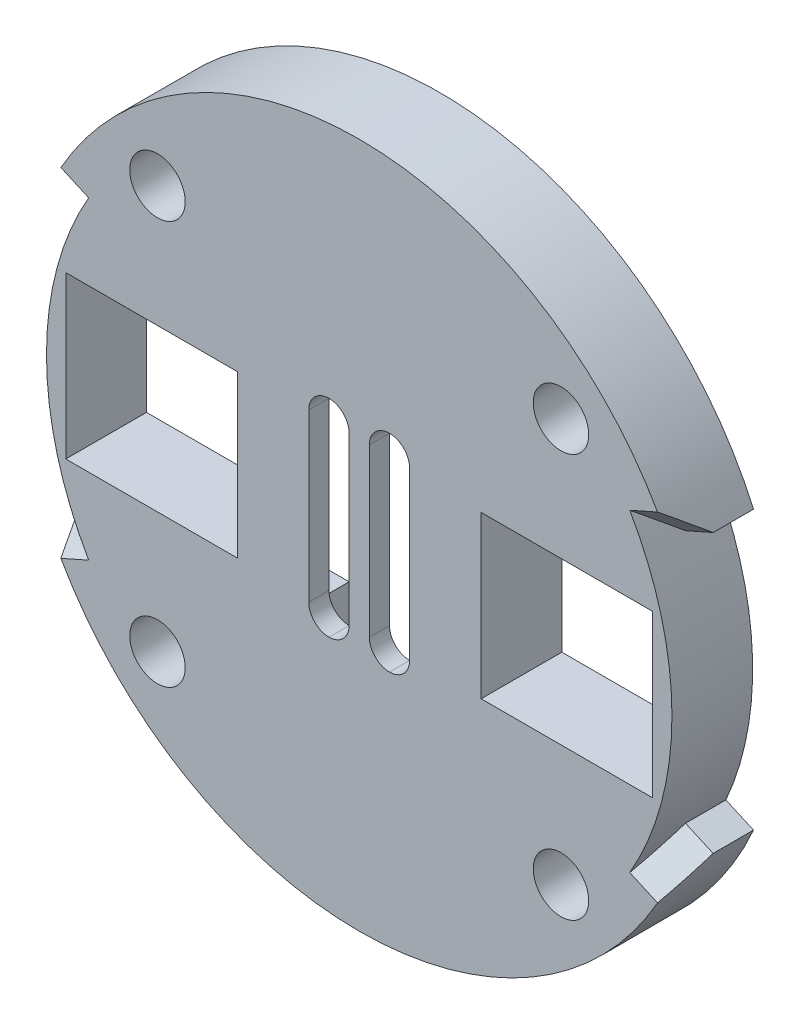
SolidWorks part; units mm, degrees
ref_plane "Front Plane" through (0, 0, 0) normal (0, 0, 1) x (1, 0, 0)
ref_plane "Top Plane" through (0, 0, 0) normal (0, 1, 0) x (1, 0, 0)
ref_plane "Right Plane" through (0, 0, 0) normal (1, 0, 0) x (0, 0, -1)
sketch "Sketch1" plane through (0, 0, 0) normal (0, 0, 1) x (1, 0, 0)
  line L2 (-32, 13.3673) -> (-29.2571, 12.1521)
  line L3 (-32, -14.1774) -> (-29.2571, -12.9622)
  line L4 (30.1714, -14.1774) -> (27.4286, -12.9622)
  line L5 (30.1714, 13.3673) -> (27.4286, 12.1521)
  arc A0 (-32, -14.1774) -> (30.1714, -14.1774) centre (-0.9143, -0.4051) ccw
  arc A1 (-29.2571, 12.1521) -> (-29.2571, -12.9622) centre (-0.9143, -0.4051) ccw
  arc A2 (27.4286, 12.1521) -> (27.4286, -12.9622) centre (-0.9143, -0.4051) cw
  arc A3 (30.1714, 13.3673) -> (-32, 13.3673) centre (-0.9143, -0.4051) ccw
  point P9 (-32, 0)
  dimension "D1" = 34
  dimension "D2" = 31
extrude "Boss-Extrude1" add sketch "Sketch1" along normal blind 8
ref_plane "Plane1" through (0, 0, 8) normal (0, 0, 1) x (1, 0, 0)
sketch "Sketch3" plane through (0, 0, 8) normal (0, 0, 1) x (1, 0, 0)
  line L0 (-0.9143, 33.5949) -> (-0.9143, -34.4051)
  line L1 (-31.9143, -0.4051) -> (30.0857, -0.4051)
  line L4 (-30, 7.5949) -> (-30, -8.4051)
  line L20 (-30, 7.5949) -> (-13, 7.5949)
  line L21 (-13, 7.5949) -> (-13, -8.4051)
  line L22 (-13, -8.4051) -> (-30, -8.4051)
  line L24 (11.1714, 7.5949) -> (11.1714, -8.4051)
  line L30 (28.1714, 7.5949) -> (11.1714, 7.5949)
  line L31 (28.1714, 7.5949) -> (28.1714, -8.4051)
  line L32 (11.1714, -8.4051) -> (28.1714, -8.4051)
  arc A0 (30.1714, 13.3673) -> (-32, 13.3673) centre (-0.9143, -0.4051) ccw construction
  arc A1 (-32, -14.1774) -> (30.1714, -14.1774) centre (-0.9143, -0.4051) ccw construction
  arc A3 (-29.2571, 12.1521) -> (-29.2571, -12.9622) centre (-0.9143, -0.4051) ccw construction
  arc A4 (27.4286, -12.9622) -> (27.4286, 12.1521) centre (-0.9143, -0.4051) ccw construction
  circle A5 centre (19.0857, 19.5949) radius 1.5
  circle A6 centre (19.0857, 19.5949) radius 2.75
  circle A7 centre (19.0857, -20.4051) radius 2.75
  circle A8 centre (-20.9143, 19.5949) radius 1.5
  circle A10 centre (-20.9143, 19.5949) radius 2.75
  circle A17 centre (19.0857, -20.4051) radius 1.5
  circle A18 centre (-20.9143, -20.4051) radius 2.75
  circle A19 centre (-20.9143, -20.4051) radius 1.5
  point P16 (0, 0)
  point P25 (-0.9143, -0.4051)
  dimension "D7" = 17
  dimension "D2" = 8
  dimension "D3" = 16
extrude "Cut-Extrude1" cut sketch "Sketch3" against normal blind 8 contours L4 | L4 | L24 L32 L31 L30 region at (-21.5, 3.5949, 8) region at (-21.5, -4.4051, 8)
extrude "Cut-Extrude3" cut sketch "Sketch3<5>" against normal blind 8 contours A8 | A19 | A17 | A5 region at (-20.9143, 19.5949, 8) region at (19.0857, -20.4051, 8) region at (-20.9143, -20.4051, 8)
sketch "Sketch3<5>" plane through (0, 0, 8) normal (0, 0, 1) x (1, 0, 0) same geometry as "Sketch3"
extrude "Cut-Extrude4" cut sketch "Sketch3<6>" against normal blind 6 contours A10 A8 | A6 A18 | A19 | A7 region at (16.4135, 19.5949, 8) region at (-23.5865, 19.5949, 8) region at (-23.5865, -20.4051, 8)
sketch "Sketch3<6>" plane through (0, 0, 8) normal (0, 0, 1) x (1, 0, 0) same geometry as "Sketch3"
chamfer "Chamfer1" distance 4 angle 40 4 edges at (28.8, -13.5698, 8) (28.8, 12.7597, 8) (-30.6286, -13.5698, 8) (-30.6286, 12.7597, 8) first distance on face at (28.8, -13.5698, 4) first distance on face at (28.8, 12.7597, 4) first distance on face at (-30.6286, -13.5698, 4) first distance on face at (-30.6286, 12.7597, 4)
sketch "Sketch4" plane through (0, 0, 0) normal (0, 0, 1) x (1, 0, 0)
  line L0 (-0.9143, 33.5949) -> (-0.9143, -34.4051)
  line L1 (8.0857, 29.5949) -> (-9.9143, 29.5949)
  line L2 (8.0857, 29.5949) -> (8.0857, -30.4051)
  line L3 (8.0857, -30.4051) -> (-9.9143, -30.4051)
  line L4 (-9.9143, 29.5949) -> (-9.9143, -30.4051)
  line L5 (28.1714, -0.4051) -> (-30, -0.4051)
  line L8 (28.1714, 7.5949) -> (28.1714, -8.4051) construction
  line L9 (-30, 7.5949) -> (-30, -8.4051) construction
  arc A0 (30.1714, 13.3673) -> (-32, 13.3673) centre (-0.9143, -0.4051) ccw construction
  arc A1 (-32, -14.1774) -> (30.1714, -14.1774) centre (-0.9143, -0.4051) ccw construction
  dimension "D1" = 18
  dimension "D2" = 60
  dimension "D3" = 9
  dimension "D4" = 30
extrude "Cut-Extrude6" cut sketch "Sketch4" along normal blind 6 contours L5 L0 L1 L4 | L5 L2 L1 L0 | L5 L0 L3 L2 | L5 L4 L3 L0 region at (3.5857, 14.5949, 0) region at (-5.4143, 14.5949, 0) region at (3.5857, -15.4051, 0) region at (-5.4143, -15.4051, 0)
sketch "Sketch5" plane through (0, 0, 0) normal (0, 0, 1) x (1, 0, 0)
  line L11 (0.0857, -10.6551) -> (4.0857, -10.6551)
  line L12 (4.0857, 9.8449) -> (4.0857, -10.6551)
  line L13 (0.0857, 9.8449) -> (4.0857, 9.8449)
  line L14 (0.0857, 9.8449) -> (0.0857, -10.6551)
  line L15 (-1.9143, 9.8449) -> (-1.9143, -10.6551)
  line L16 (-1.9143, 9.8449) -> (-5.9143, 9.8449)
  line L17 (-5.9143, 9.8449) -> (-5.9143, -10.6551)
  line L18 (-1.9143, -10.6551) -> (-5.9143, -10.6551)
extrude "Cut-Extrude8" cut sketch "Sketch5" along normal blind 8 contours L13 L14 L11 L12 | L18 L15 L16 L17 region at (2.0857, -0.4051, 0) region at (-3.9143, -0.4051, 0)
fillet "Fillet1" radius 2 8 edges at (0.0857, -10.6551, 7) (4.0857, -10.6551, 7) (4.0857, 9.8449, 7) (0.0857, 9.8449, 7) (-1.9143, -10.6551, 7) (-5.9143, -10.6551, 7) (-1.9143, 9.8449, 7) (-5.9143, 9.8449, 7)
ref_plane "Plane2" through (0, 0, 0) normal (0, 0, -1) x (-1, 0, 0)
sketch "Sketch6" plane through (0, 0, 0) normal (0, 0, -1) x (-1, 0, 0)
  line L0 (-8.0857, 29.5949) -> (-8.0857, -30.4051) construction
  line L3 (11.9143, 12.0949) -> (-10.0857, 12.0949)
  line L4 (11.9143, 12.0949) -> (11.9143, -12.9051)
  line L5 (11.9143, -12.9051) -> (-10.0857, -12.9051)
  line L6 (-10.0857, 12.0949) -> (-10.0857, -12.9051)
  point P16 (0.9143, -0.4051)
  dimension "D3" = 2
  dimension "D1" = 22
  dimension "D2" = 25
extrude "Cut-Extrude10" cut sketch "Sketch6" against normal blind 2
